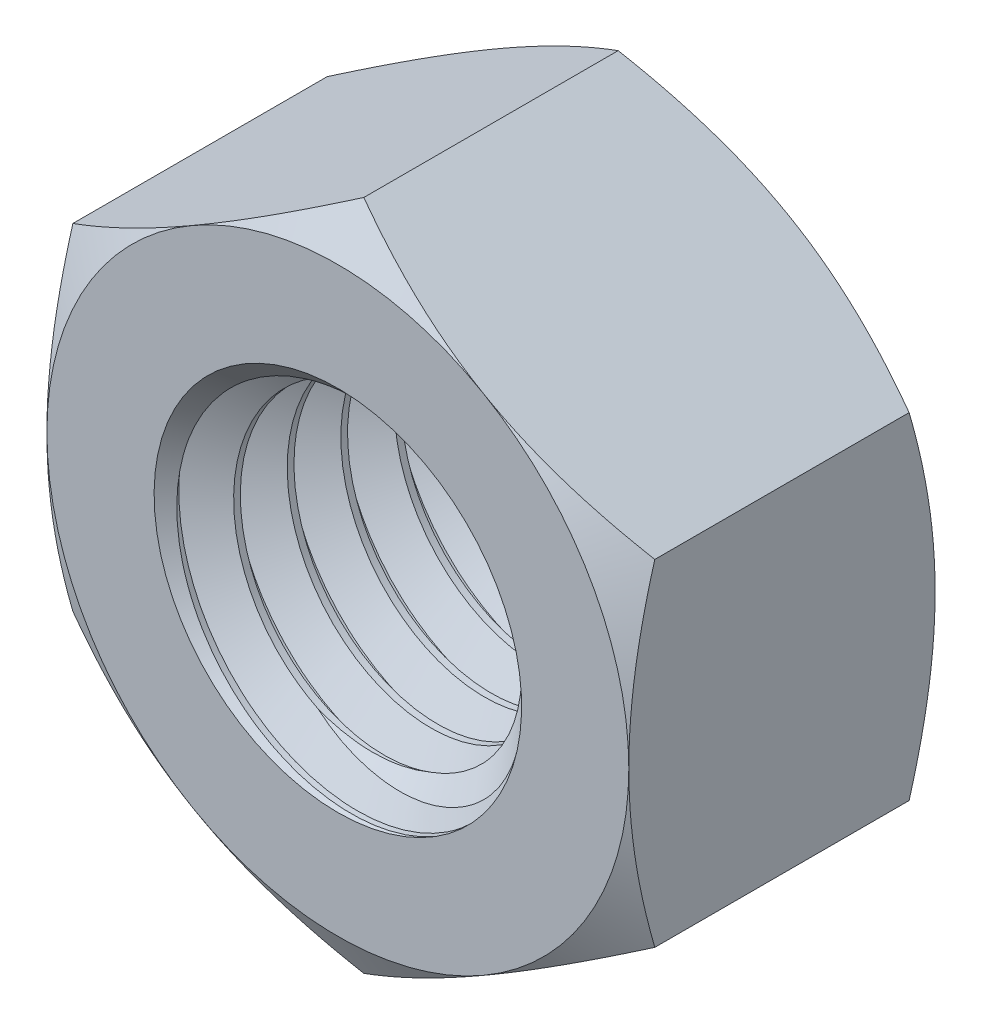
SolidWorks part; units mm, degrees
ref_plane "Front" through (0, 0, 0) normal (0, 0, 1) x (1, 0, 0)
ref_plane "Top" through (0, 0, 0) normal (0, 1, 0) x (1, 0, 0)
ref_plane "Right" through (0, 0, 0) normal (1, 0, 0) x (0, 0, -1)
sketch "Sketch1" plane through (0, 0, 0) normal (0, 0, 1) x (1, 0, 0)
  line L1 (-9.5, 5.4848) -> (-9.5, -5.4848)
  line L2 (-9.5, -5.4848) -> (0, -10.9697)
  line L3 (0, -10.9697) -> (9.5, -5.4848)
  line L4 (9.5, -5.4848) -> (9.5, 5.4848)
  line L5 (9.5, 5.4848) -> (0, 10.9697)
  line L6 (0, 10.9697) -> (-9.5, 5.4848)
  circle A0 centre (0, 0) radius 9.5 construction
  circle A1 centre (0, 0) radius 6 construction
  point P10 (0, 6)
  dimension "hex" = 19
  dimension "dia" = 12
extrude "Extrude1" add sketch "Sketch1" along normal mid plane 10
sketch "Sketch4" plane through (0, 0, -5) normal (0, 0, -1) x (-1, 0, 0)
  circle A0 centre (0, 0) radius 6 construction
  circle A1 centre (0, 0) radius 6
sketch "Sketch10" plane through (0, 0, 5) normal (0, 0, 1) x (1, 0, 0)
  circle A0 centre (0, 0) radius 6 construction
  circle A1 centre (0, 0) radius 6
extrude "Cut-Extrude2" cut sketch "Sketch10" against normal through all draft 45
sketch "Sketch11" plane through (0, 0, -5) normal (0, 0, -1) x (-1, 0, 0)
  circle A0 centre (0, 0) radius 6 construction
  circle A1 centre (0, 0) radius 6
extrude "Cut-Extrude3" cut sketch "Sketch11" against normal through all draft 45
sketch "Sketch13" plane through (0, 0, -5) normal (0, 0, -1) x (-1, 0, 0)
  circle A0 centre (0, 0) radius 6 construction
  circle A1 centre (0, 0) radius 6
extrude "Boss-Extrude1" add sketch "Sketch13" against normal up to vertex (10 mm away) separate body up to point (-9.5, 5.4848, 5)
curve "Helix/Spiral3" pitch 1.75 height 10 radius 6 centre (0, 0, -5) axis (0, 0, 1) start towards (0, 1, 0)
sketch "Sketch12" plane through (0, 0, 0) normal (1, 0, 0) x (0, 0, -1)
  line L0 (6.5313, 6) -> (5, 6)
  line L1 (6.5313, 6) -> (5.875, 4.8633)
  line L2 (5.875, 4.8633) -> (5.6563, 4.8633)
  line L3 (5.6563, 4.8633) -> (5, 6)
  line L4 (5.7656, 4.8633) -> (5.7656, 6) construction
  line L5 (5.3281, 5.4317) -> (6.2031, 5.4317) construction
  dimension "D1" = 60
  dimension "D2" = 0.2188
  dimension "D3" = 0.875
sweep "Cut-Sweep1" cut profiles "Sketch12" path "Helix/Spiral3" align with end faces yes
combine bodies "Combine1" operation type subtract main body 116 bodies to subtract 118
sketch "Sketch7" plane through (0, 0, 5) normal (0, 0, 1) x (1, 0, 0)
  circle A0 centre (0, 0) radius 9.5 construction
  circle A1 centre (0, 0) radius 9.5
extrude "Extrude2" cut sketch "Sketch7" against normal blind 25.4 draft 60 flip side to cut
mirror "Mirror2" about plane through (0, 0, 0) normal (0, 0, 1) of "Extrude2"
sketch "Sketch8" plane through (0, 0, 5) normal (0, 0, 1) x (1, 0, 0)
  line L0 (-4.2426, 4.2426) -> (0, 0) construction
  line L1 (0, -6.2648) -> (0, 6.2648) construction
  circle A1 centre (0, 0) radius 6 construction
  point P0 (-4.2426, 4.2426)
  dimension "D1" = 45
sketch "Sketch14" plane through (0, 0, 5) normal (0, 0, 1) x (1, 0, 0)
  line L0 (0, 0) -> (-6, 0) construction
  arc A0 (3.1841, -5.0854) -> (5.852, -1.3244) centre (0, 0) ccw construction
equation "\"D3@Helix/Spiral3\" = \"length@Extrude1\" "
equation "\"D2@Sketch12\" = \"D4@Helix/Spiral3\"*.125"
equation "\"D3@Sketch12\" = \"D4@Helix/Spiral3\"*.50"
